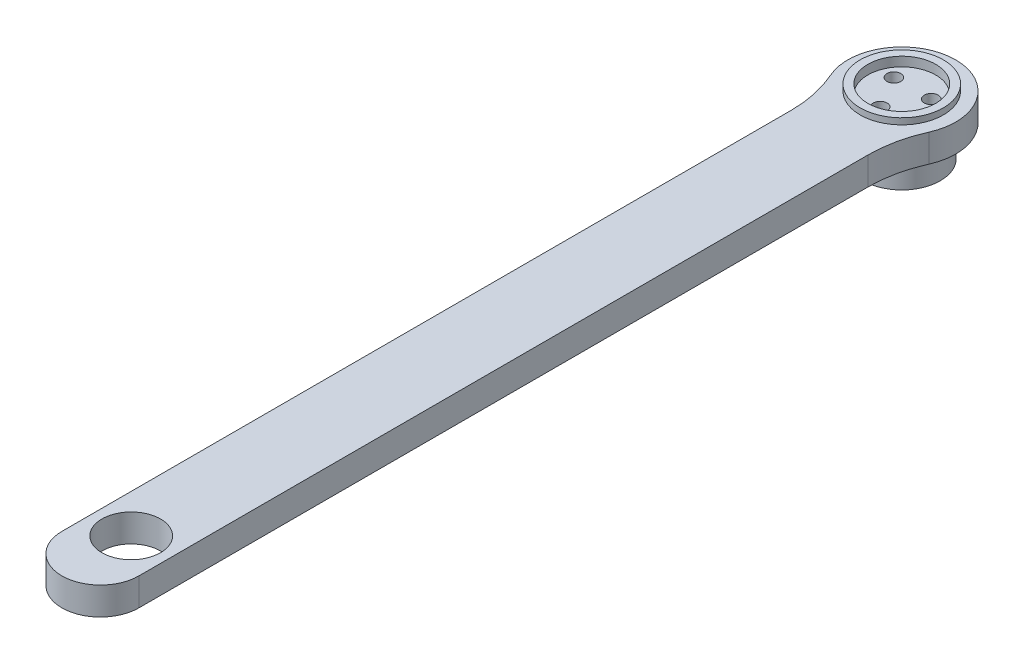
SolidWorks part; units mm, degrees
other "마크업1"
sketch "스케치14" plane through (-17.5, 12, -17.5) normal (-0.0092, 0.8478, -0.5302) x (0.9606, -0.1397, -0.2401)
sketch "스케치15" plane through (-17.5, 12, -17.5) normal (-0.0092, 0.8478, -0.5302) x (0.9606, -0.1397, -0.2401)
sketch "스케치16" plane through (-17.5, 12, -17.5) normal (-0.0092, 0.8478, -0.5302) x (0.9606, -0.1397, -0.2401)
sketch "스케치17" plane through (-17.5, 12, -17.5) normal (-0.0092, 0.8478, -0.5302) x (0.9606, -0.1397, -0.2401)
sketch "스케치18" plane through (-17.5, 11, -17.5) normal (-0.0092, 0.8478, -0.5302) x (0.9606, -0.1397, -0.2401)
sketch "스케치19" plane through (-17.5, 11, -17.5) normal (-0.0092, 0.8478, -0.5302) x (0.9606, -0.1397, -0.2401)
sketch "스케치20" plane through (-17.5, 11, -17.5) normal (-0.0092, 0.8478, -0.5302) x (0.9606, -0.1397, -0.2401)
sketch "스케치21" plane through (-17.5, 11, -17.5) normal (-0.0092, 0.8478, -0.5302) x (0.9606, -0.1397, -0.2401)
sketch "스케치22" plane through (-17.5, 11, -17.5) normal (-0.0092, 0.8478, -0.5302) x (0.9606, -0.1397, -0.2401)
sketch "스케치24" plane through (-17.5, 11, -17.5) normal (-0.0092, 0.8478, -0.5302) x (0.9606, -0.1397, -0.2401)
sketch "스케치25" plane through (-17.5, 11, -17.5) normal (-0.0092, 0.8478, -0.5302) x (0.9606, -0.1397, -0.2401)
material "7075-T6 (SN)"
ref_plane "정면" through (0, 0, 0) normal (0, 0, 1) x (1, 0, 0)
ref_plane "윗면" through (0, 0, 0) normal (0, 1, 0) x (1, 0, 0)
ref_plane "우측면" through (0, 0, 0) normal (1, 0, 0) x (0, 0, -1)
sketch "스케치1" plane through (0, 0, 0) normal (0, 1, 0) x (1, 0, 0)
  line L0 (-12.5, -260) -> (-12.5, -12.2474)
  line L1 (0, 0) -> (0, -260) construction
  line L2 (12.5, -260) -> (12.5, -12.2474)
  arc A1 (12.5, -12.2474) -> (-12.5, -12.2474) centre (0, 0) ccw
  arc A2 (-12.5, -260) -> (12.5, -260) centre (0, -260) ccw
  dimension "D2" = 35
  dimension "D3" = 25
  dimension "D4" = 260
extrude "보스-돌출1" add sketch "스케치1" along normal blind 9
sketch "스케치3" plane through (0, 9, 0) normal (0, 1, 0) x (1, 0, 0)
  circle A0 centre (0, 0) radius 13.5
  dimension "D1" = 27
extrude "보스-돌출2" add sketch "스케치3" along normal blind 2 contours A0 region at (0, 9, 0)
sketch "스케치4" plane through (0, 0, 0) normal (0, -1, 0) x (1, 0, 0)
  circle A0 centre (0, 0) radius 13.5
  dimension "D1" = 27
extrude "보스-돌출3" add sketch "스케치4" along normal blind 3 contours A0 region at (0, 0, 0)
sketch "스케치5" plane through (0, 9, 0) normal (0, 1, 0) x (1, 0, 0)
  circle A0 centre (0, -250) radius 9.5
  dimension "D1" = 19
  dimension "D2" = 250
extrude "컷-돌출2" cut sketch "스케치5" against normal through all
sketch "스케치7" plane through (0, -3, 0) normal (0, -1, 0) x (1, 0, 0)
  circle A0 centre (0, 0) radius 7
  point P3 (0, 7)
  dimension "D1" = 14
hole_wizard "M4 육각 소켓 머리 캡 나사용 카운터보어1" positions "스케치8" profile "스케치10" counterbore size "M4" standard "ISO" end condition through all
sketch "스케치8" plane through (0, -3, 0) normal (0, -1, 0) x (-1, 0, 0)
  point P0 (0, -7)
sketch "스케치10" plane through (0, -3, 7) normal (1, 0, 0) x (0, 0, -1)
  line L0 (0, 0) -> (0, 14)
  line L1 (0, 14) -> (2.25, 14)
  line L3 (2.25, 14) -> (2.25, 4.4)
  line L4 (2.25, 4.4) -> (4, 4.4)
  line L5 (4, 4.4) -> (4, 0)
  line L7 (4, 0) -> (0, 0)
  line L11 (0, -6.35) -> (0, 107.95) construction
  dimension "관통 구멍 지름" = 4.5
  dimension "관통 구멍 깊이" = 14
  dimension "카운터보어 지름" = 8
  dimension "카운터보어 깊이" = 4.4
pattern_circular "원형 패턴1" count 3 over 360 about axis through (0, 9, 0) along (0, -1, 0) of "M4 육각 소켓 머리 캡 나사용 카운터보어1"
sketch "스케치11" plane through (0, -3, 0) normal (0, -1, 0) x (1, 0, 0)
  circle A0 centre (0, 0) radius 12.5
  circle A1 centre (6.0622, -3.5) radius 4 construction
  circle A2 centre (0, 0) radius 13.5
  circle A3 centre (0, 0) radius 13.5
  circle A4 centre (-6.0622, -3.5) radius 4 construction
  circle A5 centre (0, 7) radius 4 construction
  circle A6 centre (6.0622, -3.5) radius 4
  circle A7 centre (-6.0622, -3.5) radius 4
  circle A8 centre (0, 7) radius 4
  circle M1 centre (6.0622, -3.5) radius 4
  circle M2 centre (-6.0622, -3.5) radius 4
  circle M3 centre (0, 7) radius 4
  dimension "D1" = 25
  dimension "D2" = 0
extrude "보스-돌출4" add sketch "스케치11" along normal blind 7 contours A0 M1 M3 M2 region at (0, -3, 0)
sketch "스케치13" plane through (0, 11, 0) normal (0, 1, 0) x (1, 0, 0)
  circle A0 centre (0, 0) radius 11
  dimension "D1" = 22
extrude "컷-돌출3" cut sketch "스케치13" against normal blind 3
fillet "필렛1" radius 40 2 edges at (12.5, 4.5, 12.2474) (-12.5, 4.5, 12.2474)
sketch "스케치23" plane through (0, -10, 0) normal (0, -1, 0) x (1, 0, 0)
  circle A0 centre (0, 0) radius 11
  dimension "D1" = 22
extrude "컷-돌출4" [suppressed] cut sketch "스케치23" against normal blind 5
